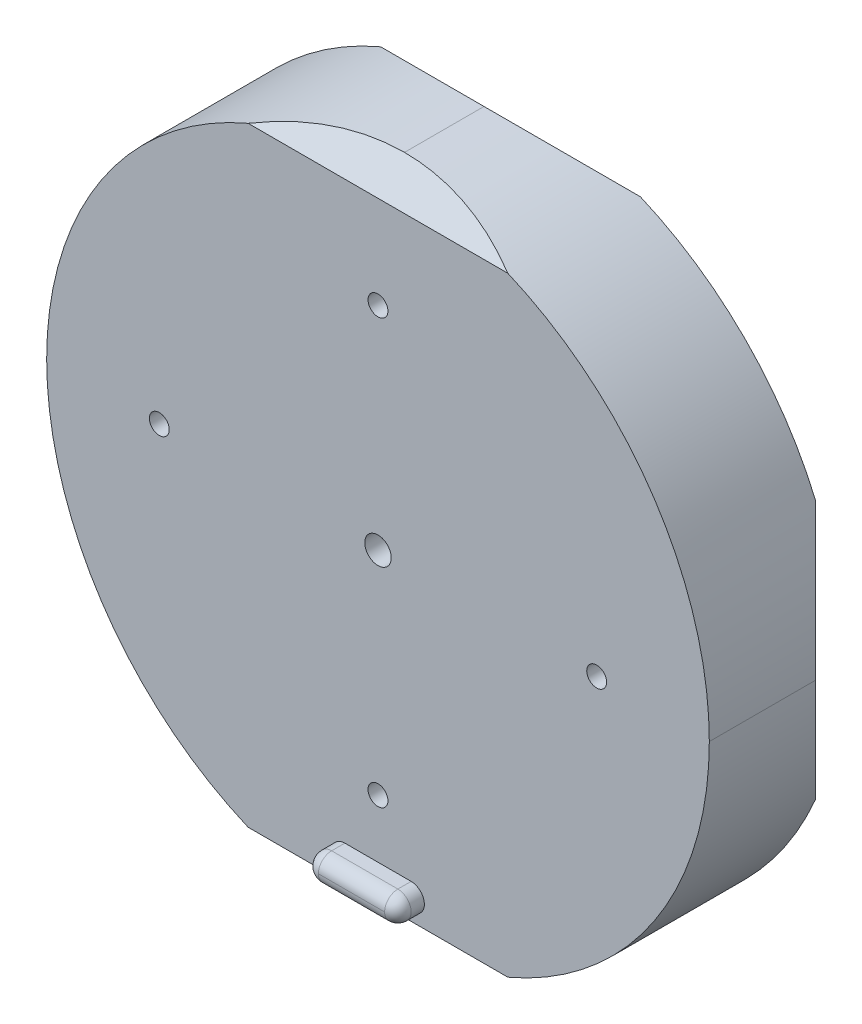
SolidWorks part; units mm, degrees
ref_plane "Front Plane" through (0, 0, 0) normal (0, 0, 1) x (1, 0, 0)
ref_plane "Top Plane" through (0, 0, 0) normal (0, 1, 0) x (1, 0, 0)
ref_plane "Right Plane" through (0, 0, 0) normal (1, 0, 0) x (0, 0, -1)
sketch "Sketch9" plane through (0, 0, 0) normal (0, 0, -1) x (-1, 0, 0)
  line L0 (-99.4869, 20.5) -> (13.5233, 20.5) construction
  line L1 (-42.5, 50.5202) -> (-42.5, -6.8796) construction
  line L2 (-59.2, 24.3) -> (-48.0118, 24.5)
  line L3 (-67.5, 45.5) -> (-17.5, 45.5)
  line L4 (-67.5, 45.5) -> (-67.5, -4.5)
  line L5 (-67.5, -4.5) -> (-17.5, -4.5)
  line L6 (-17.5, 45.5) -> (-17.5, -4.5)
  line L7 (-46.5, 26.0118) -> (-46.3, 37.2)
  line L8 (-25.8, 24.3) -> (-36.9882, 24.5)
  line L9 (-38.5, 26.0118) -> (-38.7, 37.2)
  line L10 (-59.2, 16.7) -> (-48.0118, 16.5)
  line L11 (-46.5, 14.9882) -> (-46.3, 3.8)
  line L12 (-38.5, 14.9882) -> (-38.7, 3.8)
  line L13 (-25.8, 16.7) -> (-36.9882, 16.5)
  arc A0 (-59.2, 24.3) -> (-59.2, 16.7) centre (-59.2, 20.5) ccw
  arc A1 (-48.0118, 24.5) -> (-46.5, 26.0118) centre (-47.9381, 25.9381) ccw
  arc A2 (-38.7, 37.2) -> (-46.3, 37.2) centre (-42.5, 37.2) ccw
  arc A3 (-25.8, 24.3) -> (-25.8, 16.7) centre (-25.8, 20.5) cw
  arc A4 (-36.9882, 24.5) -> (-38.5, 26.0118) centre (-37.0619, 25.9381) cw
  arc A5 (-38.7, 3.8) -> (-46.3, 3.8) centre (-42.5, 3.8) cw
  arc A6 (-48.0118, 16.5) -> (-46.5, 14.9882) centre (-47.9381, 15.0619) cw
  arc A7 (-36.9882, 16.5) -> (-38.5, 14.9882) centre (-37.0619, 15.0619) ccw
  dimension "D5" = 7.6
  dimension "D6" = 7.6
  dimension "D11" = 1.44
  dimension "D1" = 50
  dimension "D2" = 50
  dimension "D3" = 25
  dimension "D4" = 25
  dimension "D7" = 11.19
  dimension "D10" = 11.19
  dimension "D12" = 4
  dimension "D13" = 4
sketch "Sketch10" plane through (0, 0, 0) normal (0, 0, -1) x (-1, 0, 0)
  line L1 (-67.5, 45.5) -> (-17.5, 45.5)
  line L2 (-67.5, 45.5) -> (-67.5, -4.5)
  line L3 (-67.5, -4.5) -> (-17.5, -4.5)
  line L4 (-17.5, 45.5) -> (-17.5, -4.5)
extrude "Boss-Extrude7" add sketch "Sketch10" against normal blind 5
extrude "Boss-Extrude8" add sketch "Sketch9" along normal blind 5
sketch "Sketch11" plane through (0, 0, 0) normal (0, 0, -1) x (-1, 0, 0)
  line L0 (-65.7628, 20.5) -> (-18.549, 20.5) construction
  line L1 (-42.5, 43.9004) -> (-42.5, -3.5887) construction
  circle A0 centre (-59, 20.5) radius 0.75
  circle A1 centre (-26, 20.5) radius 0.75
  dimension "D1" = 1.5
  dimension "D2" = 16.5
extrude "Cut-Extrude5" cut sketch "Sketch11" against normal blind 5
chamfer "Chamfer1" distance 2 angle 45 6 edges at (42.5, -4.5, 5) (17.5, 20.5, -5) (42.5, -4.5, -5) (67.5, 20.5, -5) (42.5, 45.5, -5) (42.5, 45.5, 5)
sketch "Sketch12" plane through (0, 0, 5) normal (0, 0, 1) x (1, 0, 0)
  circle A0 centre (42.5, 20.5) radius 1
  dimension "D1" = 2
extrude "Cut-Extrude6" cut sketch "Sketch12" against normal blind 10
sketch "Sketch14" plane through (0, 0, 5) normal (0, 0, 1) x (1, 0, 0)
  circle A0 centre (42.5, 36.5) radius 0.75
  circle A1 centre (42.5, 4.5) radius 0.75
  circle A2 centre (42.5, 20.5) radius 1 construction
  dimension "D1" = 16
  dimension "D2" = 16
  dimension "D3" = 1.5
  dimension "D4" = 1.5
extrude "Cut-Extrude8" cut sketch "Sketch14" against normal blind 5
sketch "Sketch15" plane through (0, 0, 5) normal (0, 0, 1) x (1, 0, 0)
  line L0 (40, -0.8877) -> (45, -0.8877) construction
  line L1 (40, 0.1123) -> (45, 0.1123)
  line L2 (40, -1.8877) -> (45, -1.8877)
  line L3 (17.5, -2.5) -> (17.5, 43.5) construction
  arc A0 (40, 0.1123) -> (40, -1.8877) centre (40, -0.8877) ccw
  arc A1 (45, -1.8877) -> (45, 0.1123) centre (45, -0.8877) ccw
  point P2 (42.5, -0.8877)
  dimension "D2" = 1
  dimension "D1" = 5
  dimension "D3" = 22.5
extrude "Boss-Extrude9" add sketch "Sketch15" along normal blind 2
fillet "Fillet1" radius 1 4 edges at (42.5, 0.1123, 7) (46, -0.8877, 7) (42.5, -1.8877, 7) (39, -0.8877, 7)
fillet "Fillet2" radius 25 4 edges at (17.5, 45.5, 0) (67.5, 45.5, 0) (67.5, -4.5, 0) (17.5, -4.5, 0)
